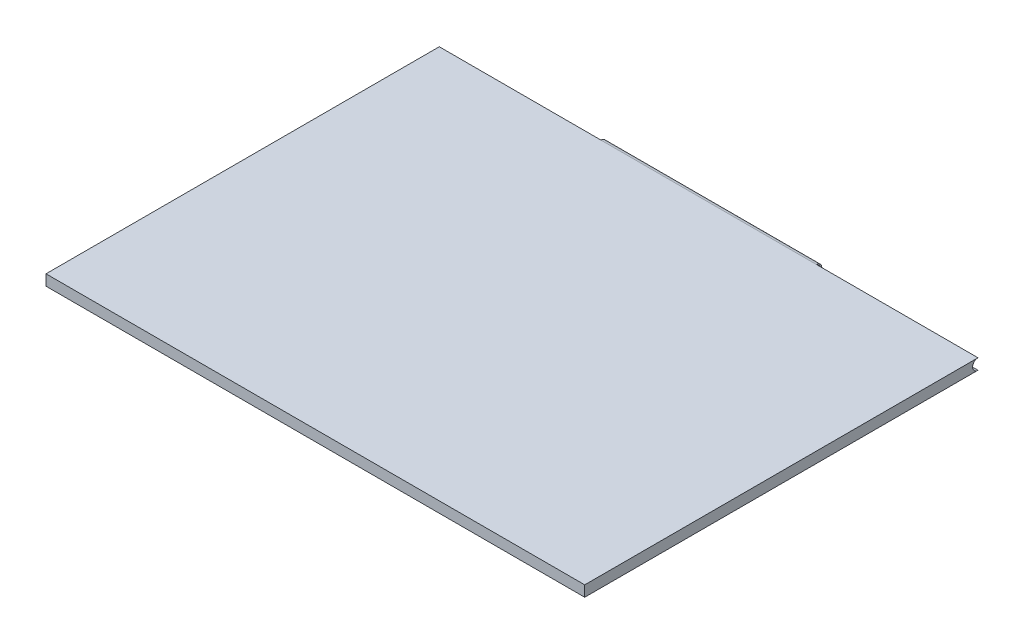
SolidWorks part; units mm, degrees
ref_plane "前视基准面" through (0, 0, 0) normal (0, 0, 1) x (1, 0, 0)
ref_plane "上视基准面" through (0, 0, 0) normal (0, 1, 0) x (1, 0, 0)
ref_plane "右视基准面" through (0, 0, 0) normal (1, 0, 0) x (0, 0, -1)
sketch "草图1" plane through (0, 0, 0) normal (0, 1, 0) x (1, 0, 0)
  line L1 (-95.2607, 80.1232) -> (104.7393, 80.1232)
  line L2 (-95.2607, 80.1232) -> (-95.2607, -65.8768)
  line L3 (-95.2607, -65.8768) -> (104.7393, -65.8768)
  line L4 (104.7393, 80.1232) -> (104.7393, -65.8768)
  dimension "D1" = 200
  dimension "D2" = 146
extrude "凸台-拉伸1" add sketch "草图1" along normal blind 4
sketch "草图3" plane through (104.7393, 0, 0) normal (1, 0, 0) x (0, 0, -1)
  line L0 (80.1232, 4) -> (80.1232, 0) construction
  circle A0 centre (80.1232, 2) radius 2
extrude "切除-拉伸1" cut sketch "草图3" against normal blind 202
extrude "拉伸-薄壁1" add sketch "草图3<2>" against normal blind 200 thin thin type one direction reverse wall 0.5
sketch "草图3<2>" plane through (104.7393, 0, 0) normal (1, 0, 0) x (0, 0, -1) same geometry as "草图3"
sketch "草图4" plane through (104.7393, 0, 0) normal (1, 0, 0) x (0, 0, -1)
  circle A0 centre (80.1232, 2) radius 2
extrude "切除-拉伸2" cut sketch "草图4" against normal blind 60
sketch "草图5" plane through (-95.2607, 0, 0) normal (-1, 0, 0) x (0, 0, 1)
  circle A0 centre (-80.1232, 2) radius 2
extrude "切除-拉伸3" cut sketch "草图5" against normal blind 60
